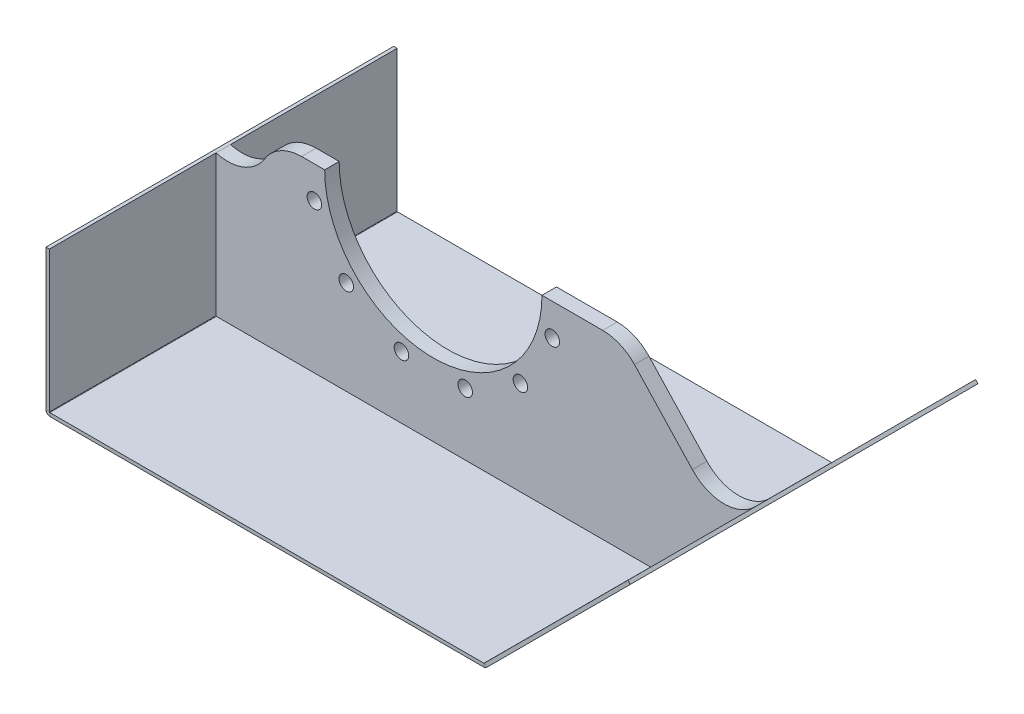
SolidWorks part; units mm, degrees
note: The reader was unsure of these and kept them because the rebuilt part matched: flange length of "Edge-Flange1", "Edge-Flange2".
material "AISI 304"
ref_plane "Front Plane" through (0, 0, 0) normal (0, 0, 1) x (1, 0, 0)
ref_plane "Top Plane" through (0, 0, 0) normal (0, 1, 0) x (1, 0, 0)
ref_plane "Right Plane" through (0, 0, 0) normal (1, 0, 0) x (0, 0, -1)
sketch "Sketch1" plane through (0, 0, 0) normal (0, 0, 1) x (1, 0, 0)
  line L0 (0, 0) -> (0, 241.3) construction
  line L1 (0, 0) -> (55.879, 208.5434) construction
  circle A0 centre (0, 0) radius 241.3
  circle A1 centre (0, 0) radius 190.5
  circle A2 centre (55.879, 208.5434) radius 12.7
  circle A3 centre (0, 0) radius 215.9 construction
  circle A4 centre (152.6644, 152.6644) radius 12.7
  circle A5 centre (208.5434, 55.879) radius 12.7
  circle A6 centre (208.5434, -55.879) radius 12.7
  circle A7 centre (152.6644, -152.6644) radius 12.7
  circle A8 centre (55.879, -208.5434) radius 12.7
  circle A9 centre (-55.879, -208.5434) radius 12.7
  circle A10 centre (-152.6644, -152.6644) radius 12.7
  circle A11 centre (-208.5434, -55.879) radius 12.7
  circle A12 centre (-208.5434, 55.879) radius 12.7
  circle A13 centre (-152.6644, 152.6644) radius 12.7
  circle A14 centre (-55.879, 208.5434) radius 12.7
  point P32 (0, 0)
  dimension "D1" = 482.6
  dimension "D2" = 381
  dimension "D3" = 431.8
  dimension "D4" = 25.4
  dimension "D6" = 15
  dimension "D5" = 12
extrude "Boss-Extrude1" add sketch "Sketch1" along normal blind 25.4
ref_plane "Plane1" through (0, 0, 12.7) normal (0, 0, -1) x (-1, 0, 0)
sketch "Sketch2" plane through (0, 0, 12.7) normal (0, 0, -1) x (-1, 0, 0)
  line L0 (0, -241.3) -> (0, -317.5)
  line L1 (0, 13.97) -> (0, -13.97) construction
  line L2 (-381, -317.5) -> (381, -317.5)
  line L3 (-381, -317.5) -> (-635, -63.5)
  line L4 (381, -317.5) -> (381, -63.5)
  line L5 (381, -190.5) -> (211.1875, 116.7284)
  line L6 (-176.3716, 164.6777) -> (-508, -190.5)
  circle A0 centre (0, 0) radius 190.5 construction
  circle A1 centre (0, 0) radius 241.3
  dimension "D5" = 381
  dimension "D8" = 482.6
  dimension "D1" = 762
  dimension "D2" = 254
  dimension "D3" = 135
  dimension "D4" = 76.2
ref_plane "Plane3" through (0, -317.5, 0) normal (0, 1, 0) x (1, 0, 0)
sketch "Sketch19" plane through (0, -317.5, 0) normal (0, 1, 0) x (1, 0, 0)
  line L0 (381, -12.7) -> (-381, -12.7) construction
  line L1 (-381, -317.5) -> (381, -317.5)
  line L2 (-381, -317.5) -> (-381, 292.1)
  line L3 (-381, 292.1) -> (381, 292.1)
  line L4 (381, -317.5) -> (381, 292.1)
  line L5 (-381, -317.5) -> (381, 292.1) construction
  line L6 (-381, 292.1) -> (381, -317.5) construction
  point P0 (0, -12.7)
  dimension "D1" = 609.6
base flange "Base-Flange1" sketch "Sketch19" thickness 6 reverse thickness direction no parameters "D1"=0.7366
edge flange "Edge-Flange1" sketch "Sketch26" flange angle 135 flange length 359.156 flange position material outside bend radius 0.7366 thickness 6 relief rectangular parameters "D6"=10
sketch "Sketch26" plane through (381, -317.5, 0) normal (0.7071, -0.7071, 0) x (0, 0, -1)
  line L2 (-317.5, 0) -> (-317.5, 356.6707)
  line L3 (-317.5, 356.6707) -> (292.1, 356.6707)
  line L4 (292.1, 356.6707) -> (292.1, 0)
  line L7 (-317.5, 0) -> (292.1, 0) construction
  line L8 (-317.5, 0) -> (292.1, 0)
bend "EdgeBend1" bend radius 0.7366 bend angle 45 parameters "D5"=1
edge flange "Edge-Flange2" sketch "Sketch29" flange angle 90 flange length 254 flange position material outside bend radius 0.7366 thickness 6 relief rectangular parameters "D6"=10
sketch "Sketch29" plane through (-381, -317.5, 0) normal (-1, 0, 0) x (0, 0, 1)
  line L2 (-292.1, 0) -> (-292.1, 248)
  line L3 (-292.1, 248) -> (317.5, 248)
  line L4 (317.5, 248) -> (317.5, 0)
  line L7 (-292.1, 0) -> (317.5, 0) construction
  line L8 (-292.1, 0) -> (317.5, 0)
bend "EdgeBend2" bend radius 0.7366 bend angle 90 parameters "D5"=2
extrude "Boss-Extrude2" add sketch "Sketch2" along normal blind 12.7 and the other way blind 12.7
fillet "Fillet1" radius 76.2 2 edges at (-381, -190.5, 12.7) (508, -190.5, 12.7)
sketch "Sketch30" plane through (0, 0, 0) normal (0, 0, -1) x (-1, 0, 0)
  line L0 (-190.5, 0) -> (-330.1307, 0)
  line L1 (335.28, 0) -> (-335.28, 0) construction
  line L2 (-176.3716, 164.6777) -> (-454.1829, -132.8612) construction
  line L3 (-176.3716, 164.6777) -> (-508, -190.5) construction
  line L4 (190.5, 0) -> (275.7061, 0)
  line L5 (293.9138, -32.9418) -> (211.1875, 116.7284) construction
  circle A0 centre (0, 0) radius 190.5 construction
  circle A1 centre (0, 0) radius 190.5 construction
  circle A2 centre (0, 0) radius 241.3
  circle A3 centre (0, 0) radius 190.5
  circle M1 centre (0, 0) radius 190.5
  circle M2 centre (-55.879, 208.5434) radius 12.7
  circle M3 centre (-152.6644, 152.6644) radius 12.7
  circle M4 centre (-208.5434, 55.879) radius 12.7
  circle M11 centre (208.5434, 55.879) radius 12.7
  circle M12 centre (152.6644, 152.6644) radius 12.7
  circle M13 centre (55.879, 208.5434) radius 12.7
  line M19 (293.9138, -32.9418) -> (211.1875, 116.7284)
  arc M20 (211.1875, 116.7284) -> (-176.3716, 164.6777) centre (0, 0) ccw
  line M21 (-176.3716, 164.6777) -> (-454.1829, -132.8612)
extrude "Cut-Extrude1" cut sketch "Sketch30" against normal through all contours A2 L0 M21 | L4 A2 L0 M20 M1 M3 M11 M13 M12 M4 M2 | A2 L4 M19 normal cut yes
fillet "Fillet3" radius 76.2 2 edges at (-275.7061, 0, 12.7) (330.1307, 0, 12.7)
sketch "Lignes de pliage1" [suppressed] plane through (0, 0, 0) normal (0, 1, 0) x (1, 0, 0)
sketch "Cube de visualisation1" [suppressed] plane through (0, 0, 0) normal (0, 1, 0) x (1, 0, 0)
sheet metal parameters "Sheet-Metal14" thickness 6 parameters "D1"=0.7366
flat pattern "Flat-Pattern14" [suppressed]
sketch "Lignes de pliage2" plane through (0, 0, 0) normal (0, 1, 0) x (1, 0, 0)
sketch3d "Cube de visualisation2" [suppressed]
  line L0 (-381, 279.4, 0) -> (381, 279.4, 0) construction
  line L1 (-381, -330.2, 0) -> (381, -330.2, 0) construction
  line L2 (-381, 279.4, 0) -> (-381, -330.2, 0) construction
  line L3 (381, 279.4, 0) -> (381, -330.2, 0) construction
sheet metal parameters "Sheet-Metal15" thickness 6 parameters "D1"=0.7366
flat pattern "Flat-Pattern14"
sketch "Lignes de pliage2" plane through (0, -317.5, 0) normal (0, 1, 0) x (1, 0, 0)
  line L0 (382.1622, -330.2) -> (382.1622, 279.4) construction
  line L1 (382.1622, -330.2) -> (382.1622, 279.4) construction
sketch3d "Cube de visualisation2" [suppressed]
  line L0 (739.9952, 279.4, 0) -> (-381, 279.4, 0) construction
  line L1 (739.9952, -330.2, 0) -> (-381, -330.2, 0) construction
  line L2 (739.9952, 279.4, 0) -> (739.9952, -330.2, 0) construction
  line L3 (-381, 279.4, 0) -> (-381, -330.2, 0) construction
bend of the flat pattern "Flatten-<EdgeBend1>1"
sheet metal parameters "Sheet-Metal16" thickness 6 parameters "D1"=0.7366
flat pattern "Flat-Pattern14"
sketch "Lignes de pliage2" plane through (0, -317.5, 0) normal (0, 1, 0) x (1, 0, 0)
  line L0 (382.1622, -317.5) -> (382.1622, 292.1) construction
  line L1 (382.1622, -317.5) -> (382.1622, 292.1) construction
  line L2 (-383.1981, 292.1) -> (-383.1981, -317.5) construction
  line L3 (-383.1981, 292.1) -> (-383.1981, -317.5) construction
sketch3d "Cube de visualisation2" [suppressed]
  line L0 (739.9952, 292.1, 0) -> (-633.3962, 292.1, 0) construction
  line L1 (739.9952, -317.5, 0) -> (-633.3962, -317.5, 0) construction
  line L2 (739.9952, 292.1, 0) -> (739.9952, -317.5, 0) construction
  line L3 (-633.3962, 292.1, 0) -> (-633.3962, -317.5, 0) construction
bend of the flat pattern "Flatten-<EdgeBend1>1"
bend of the flat pattern "Flatten-<EdgeBend2>1"
sheet metal parameters "Sheet-Metal22" thickness 6 parameters "D1"=0.7366
flat pattern "Flat-Pattern14"
sketch "Lignes de pliage2" plane through (0, -317.5, 0) normal (0, 1, 0) x (1, 0, 0)
  line L0 (382.1622, -317.5) -> (382.1622, 292.1) construction
  line L1 (382.1622, -317.5) -> (382.1622, 292.1) construction
  line L2 (-383.1981, 292.1) -> (-383.1981, -317.5) construction
  line L3 (-383.1981, 292.1) -> (-383.1981, -317.5) construction
sketch3d "Cube de visualisation2" [suppressed]
  line L0 (739.9952, 292.1, 0) -> (-633.3962, 292.1, 0) construction
  line L1 (739.9952, -317.5, 0) -> (-633.3962, -317.5, 0) construction
  line L2 (739.9952, 292.1, 0) -> (739.9952, -317.5, 0) construction
  line L3 (-633.3962, 292.1, 0) -> (-633.3962, -317.5, 0) construction
bend of the flat pattern "Flatten-<EdgeBend1>1"
bend of the flat pattern "Flatten-<EdgeBend2>1"
sheet metal parameters "Sheet-Metal23" thickness 6 parameters "D1"=0.7366
flat pattern "Flat-Pattern14"
sketch "Lignes de pliage2" plane through (0, -317.5, 0) normal (0, 1, 0) x (1, 0, 0)
  line L0 (382.1622, -317.5) -> (382.1622, 292.1) construction
  line L1 (382.1622, -317.5) -> (382.1622, 292.1) construction
  line L2 (-383.1981, 292.1) -> (-383.1981, -317.5) construction
  line L3 (-383.1981, 292.1) -> (-383.1981, -317.5) construction
sketch3d "Cube de visualisation2" [suppressed]
  line L0 (739.9952, 292.1, 0) -> (-633.3962, 292.1, 0) construction
  line L1 (739.9952, -317.5, 0) -> (-633.3962, -317.5, 0) construction
  line L2 (739.9952, 292.1, 0) -> (739.9952, -317.5, 0) construction
  line L3 (-633.3962, 292.1, 0) -> (-633.3962, -317.5, 0) construction
bend of the flat pattern "Flatten-<EdgeBend1>1"
bend of the flat pattern "Flatten-<EdgeBend2>1"
